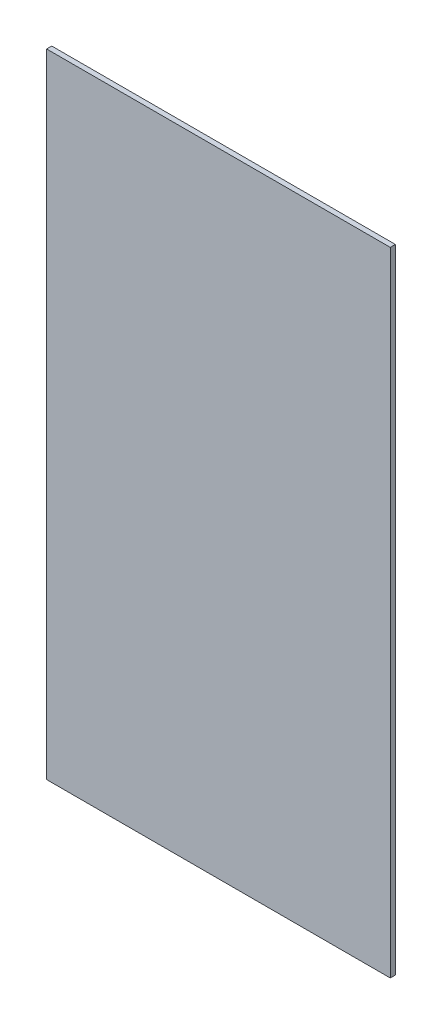
SolidWorks part; units mm, degrees
material "1060 Alloy"
ref_plane "Front Plane" through (0, 0, 0) normal (0, 0, 1) x (1, 0, 0)
ref_plane "Top Plane" through (0, 0, 0) normal (0, 1, 0) x (1, 0, 0)
ref_plane "Right Plane" through (0, 0, 0) normal (1, 0, 0) x (0, 0, -1)
sketch "Sketch1" plane through (0, 0, 0) normal (0, 0, 1) x (1, 0, 0)
  line L1 (-77.5, 142.695) -> (77.5, 142.695)
  line L2 (-77.5, 142.695) -> (-77.5, -142.695)
  line L3 (-77.5, -142.695) -> (77.5, -142.695)
  line L4 (77.5, 142.695) -> (77.5, -142.695)
  line L5 (-77.5, 142.695) -> (77.5, -142.695) construction
  line L6 (-77.5, -142.695) -> (77.5, 142.695) construction
  point P0 (0, 0)
  dimension "D1" = 155
  dimension "D2" = 285.39
extrude "Boss-Extrude1" add sketch "Sketch1" along normal blind 2.305
